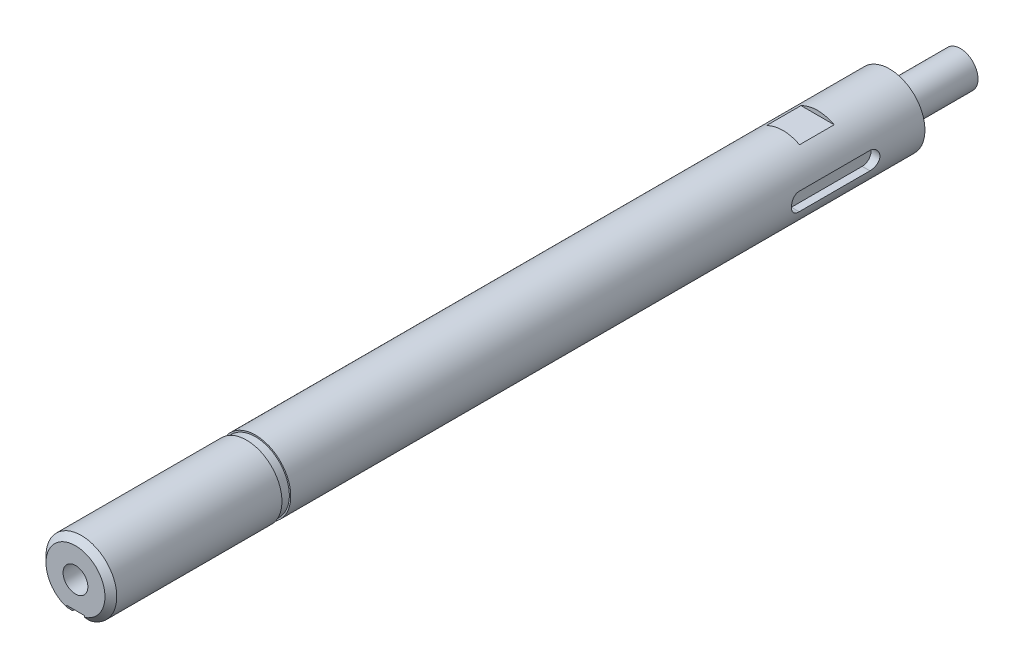
SolidWorks part; units mm, degrees
material "1.2210 (115CrV3)"
ref_plane "Front Plane" through (0, 0, 0) normal (0, 0, 1) x (1, 0, 0)
ref_plane "Top Plane" through (0, 0, 0) normal (0, 1, 0) x (1, 0, 0)
ref_plane "Right Plane" through (0, 0, 0) normal (1, 0, 0) x (0, 0, -1)
sketch "Sketch1" plane through (0, 0, 0) normal (1, 0, 0) x (0, 0, -1)
  line L0 (0, 0) -> (0, 6)
  line L8 (107.1, 6) -> (107.1, 0)
  line L9 (107.1, 0) -> (0, 0)
  line L10 (-38.6361, 0) -> (0, 0) construction
  line L18 (107.1, 6) -> (0, 6)
  dimension "D1" = 107.1
  dimension "D16" = 12
revolve "Revolve1" add sketch "Sketch1" angle 360 about L10
ref_plane "Plane3" through (0, 0, -107.1) normal (0, 0, -1) x (-1, 0, 0)
sketch "Sketch18" plane through (0, 0, 0) normal (0, 0, 1) x (1, 0, 0)
  circle A0 centre (0, 0) radius 6
  dimension "D1" = 12
extrude "Boss-Extrude1" add sketch "Sketch18" along normal blind 72.5
sketch "Sketch19" plane through (0, 0, 0) normal (0, 1, 0) x (1, 0, 0)
  line L0 (0, -63.9) -> (0, -51.9) construction
  line L1 (-1.5, -63.9) -> (-1.5, -51.9)
  line L2 (1.5, -63.9) -> (1.5, -51.9)
  line L3 (-6, -72.5) -> (6, -72.5) construction
  arc A0 (-1.5, -63.9) -> (1.5, -63.9) centre (0, -63.9) ccw
  arc A1 (1.5, -51.9) -> (-1.5, -51.9) centre (0, -51.9) ccw
  point P2 (0, -57.9)
  dimension "D1" = 3
  dimension "D2" = 12
  dimension "D3" = 8.6
extrude "Cut-Extrude4" cut sketch "Sketch19" against normal up to surface (1.3095 mm away) from offset 4.5 up to face at (6, 0, -107.1) offset against normal yes
hole_wizard "M5 Tapped Hole3" positions "Sketch21" profile "Sketch20" tap size "M5" standard "ISO"
sketch "Sketch21" plane through (0, 0, 72.5) normal (0, 0, 1) x (1, 0, 0)
  point P0 (0, 0)
sketch "Sketch20" plane through (0, 0, 72.5) normal (1, 0, 0) x (0, -1, 0)
  line L0 (0, 0) -> (0, 25.2618)
  line L1 (0, 25.2618) -> (2.1, 24)
  line L2 (2.1, 24) -> (2.1, 0.9)
  line L3 (2.1, 0.9) -> (3, 0)
  line L5 (3, 0) -> (0, 0)
  line L6 (-2.1, 0.9) -> (-3, 0) construction
  line L10 (0, 25.2618) -> (-2.1, 24) construction
  line L11 (0, -6.35) -> (0, 107.95) construction
  dimension "Tap Drill Dia." = 4.2
  dimension "Tap Drill Depth" = 24
  dimension "Near C'Sink Dia." = 6
  dimension "Near C'Sink Angle" = 90
  dimension "Drill Angle" = 118
cosmetic thread "Hole Thread18" parameters "D1"=20, "D2"=5
sketch "Sketch22" plane through (0, 0, -107.1) normal (0, 0, -1) x (-1, 0, 0)
  circle A1 centre (0, 0) radius 6
  circle A2 centre (0, 0) radius 6
  dimension "D1" = 0
extrude "Boss-Extrude2" add sketch "Sketch22" along normal offset from surface (21.4 mm away) 21.4 up to plane "Plane3"
cosmetic thread "Cosmetic Thread1" [suppressed]
chamfer "Chamfer2" distance 1 angle 45 1 edges at (6, 0, 72.5)
sketch "Sketch25" plane through (0, 0, 72.5) normal (0, 0, 1) x (1, 0, 0)
  line L0 (-1.5, -7.5) -> (-1.5, -4.5)
  line L1 (-1.5, -7.5) -> (1.5, -7.5)
  line L2 (-1.5, -4.5) -> (1.5, -4.5)
  line L3 (1.5, -7.5) -> (1.5, -4.5)
  line L4 (-1.5, -7.5) -> (1.5, -4.5) construction
  line L5 (-1.5, -4.5) -> (1.5, -7.5) construction
  line L6 (0, 0) -> (0, -6) construction
  circle A0 centre (0, 0) radius 6 construction
  point P1 (0, -6)
  dimension "D1" = 3
extrude "Cut-Extrude5" cut sketch "Sketch25" against normal blind 70
fillet "Fillet2" radius 1.5 2 edges at (1.5, -5.1547, 2.5) (-1.5, -5.1547, 2.5)
sketch "Sketch30" plane through (0, 0, -128.5) normal (0, 0, -1) x (-1, 0, 0)
  circle A0 centre (0, 0) radius 3
  dimension "D1" = 6
extrude "Cut-Extrude10" cut sketch "Sketch30" against normal blind 12 flip side to cut
sketch "Sketch31" plane through (0, 0, 0) normal (1, 0, 0) x (0, 0, -1)
  line L0 (104.3, -28.1196) -> (104.3, -5.3)
  line L1 (104.3, -28.1196) -> (98.43, -28.1196)
  line L2 (104.3, -5.3) -> (98.43, -5.3)
  line L3 (98.43, -28.1196) -> (98.43, -5.3)
  line L4 (104.3, -28.1196) -> (98.43, -5.3) construction
  line L5 (104.3, -5.3) -> (98.43, -28.1196) construction
  line L6 (104.3, 28.1555) -> (104.3, 5.3)
  line L7 (104.3, 28.1555) -> (98.43, 28.1555)
  line L8 (104.3, 5.3) -> (98.43, 5.3)
  line L9 (98.43, 28.1555) -> (98.43, 5.3)
  line L10 (104.3, 28.1555) -> (98.43, 5.3) construction
  line L11 (104.3, 5.3) -> (98.43, 28.1555) construction
  line L12 (98.43, -5.3) -> (98.43, 5.3) construction
  line L13 (98.43, 5.3) -> (98.5751, 6.4403) construction
  line L14 (0, 0) -> (98.43, 0) construction
  line L15 (116.5, -6) -> (116.5, 6) construction
  point P1 (101.365, -16.7098)
  point P2 (101.365, 16.7278)
  dimension "D1" = 5.87
  dimension "D2" = 12.2
  dimension "D3" = 10.6
extrude "Cut-Extrude11" cut sketch "Sketch31" against normal through all both and the other way through all
sketch "Sketch32" plane through (0, 0, 0) normal (1, 0, 0) x (0, 0, -1)
  line L0 (107.365, 0) -> (95.365, 0) construction
  line L1 (107.365, -1.5) -> (95.365, -1.5)
  line L2 (107.365, 1.5) -> (95.365, 1.5)
  line L3 (101.365, 5.3) -> (101.365, -5.3) construction
  line L4 (104.3, 5.3) -> (98.43, 5.3) construction
  arc A0 (107.365, -1.5) -> (107.365, 1.5) centre (107.365, 0) ccw
  arc A1 (95.365, 1.5) -> (95.365, -1.5) centre (95.365, 0) ccw
  point P2 (101.365, 0)
  dimension "D1" = 3
  dimension "D2" = 12
extrude "Cut-Extrude12" cut sketch "Sketch32" along normal through all from offset 4.5
ref_plane "Plane4" through (0, 0, 41.3) normal (0, 0, -1) x (-1, 0, 0)
sketch "Sketch33" plane through (0, 0, 41.3) normal (0, 0, -1) x (-1, 0, 0)
  circle A0 centre (0, 0) radius 5.75
  dimension "D1" = 11.5
extrude "Cut-Extrude13" cut sketch "Sketch33" against normal blind 1.5 from offset 50.3 flip side to cut
sketch "Sketch34" plane through (0, 0, -128.5) normal (0, 0, -1) x (-1, 0, 0)
  circle A0 centre (0, 0) radius 21.8782
extrude "Cut-Extrude14" cut sketch "Sketch34" against normal through all from offset 150 offset against normal yes
chamfer "Chamfer3" distance 1 angle 45 1 edges at (0, 6, 21.5)
hole_wizard "M5 Tapped Hole4" positions "Sketch36" profile "Sketch35" tap size "M5" standard "ISO"
sketch "Sketch36" plane through (0, 0, 21.5) normal (0, 0, 1) x (1, 0, 0)
  point P0 (0, 0)
sketch "Sketch35" plane through (0, 0, 21.5) normal (1, 0, 0) x (0, -1, 0)
  line L0 (0, 0) -> (0, 15.2618)
  line L1 (0, 15.2618) -> (2.1, 14)
  line L2 (2.1, 14) -> (2.1, 0)
  line L5 (2.1, 0) -> (0, 0)
  line L10 (0, 15.2618) -> (-2.1, 14) construction
  line L11 (0, -6.35) -> (0, 107.95) construction
  dimension "Tap Drill Dia." = 4.2
  dimension "Tap Drill Depth" = 14
  dimension "Drill Angle" = 118
move or copy body "Body-Move/Copy1" [suppressed] bodies to move or copy 120
sketch "Sketch29" [suppressed] plane through (0, 0, 107.1) normal (0, 0, 1) x (1, 0, 0)
  circle A0 centre (0, 0) radius 13.0375
ref_plane "Plane2" [suppressed] through (0, 0, 107.1) normal (0, 0, 1) x (1, 0, 0)
sketch "Sketch28" [suppressed] plane through (0, 0, -72.5) normal (0, 0, -1) x (-1, 0, 0)
  circle A0 centre (0, 0) radius 10.9947
sketch "Sketch27" [suppressed] plane through (0, 0, 128.5) normal (0, 0, 1) x (1, 0, 0)
  circle A0 centre (0, 0) radius 3
  dimension "D1" = 6
extrude "Cut-Extrude7" [suppressed] cut sketch "Sketch27" against normal blind 12 flip side to cut
extrude "Cut-Extrude8" [suppressed] cut sketch "Sketch28" against normal blind 50
equation "\"mm\"=40"
